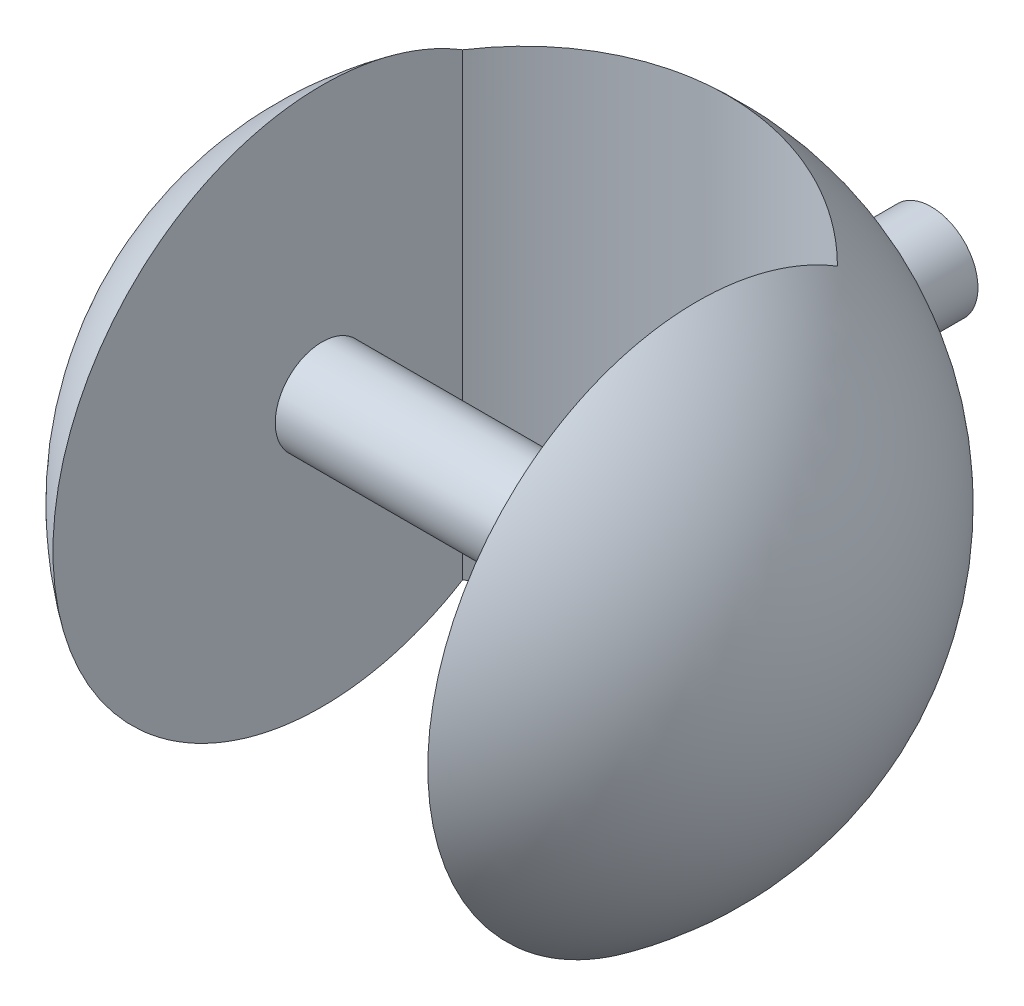
SolidWorks part; units mm, degrees
ref_plane "Front Plane" through (0, 0, 0) normal (0, 0, 1) x (1, 0, 0)
ref_plane "Top Plane" through (0, 0, 0) normal (0, 1, 0) x (1, 0, 0)
ref_plane "Right Plane" through (0, 0, 0) normal (1, 0, 0) x (0, 0, -1)
sketch "Sketch3" plane through (0, 0, 0) normal (0, 0, 1) x (1, 0, 0)
  line L0 (0, 136.0944) -> (0, -136.0944) construction
  line L1 (0, 70) -> (0, -70)
  arc A0 (0, 70) -> (0, -70) centre (0, 0) cw
  point P3 (0, 0)
  dimension "D1" = 70
revolve "Revolve1" add sketch "Sketch3" angle 360 about L0
sketch "Sketch4" plane through (0, 0, 0) normal (0, 1, 0) x (1, 0, 0)
  line L0 (-40, -70) -> (-40, 30)
  line L1 (-40, -70) -> (40, -70)
  line L3 (-40, 30) -> (40, 30)
  line L4 (40, -70) -> (40, 30)
  dimension "D2" = 100
extrude "Cut-Extrude1" cut sketch "Sketch4" against normal blind 200 and the other way blind 200
sketch "Sketch5" plane through (0, 0, -30) normal (0, 0, 1) x (1, 0, 0)
  circle A0 centre (0, 0) radius 10
extrude "Boss-Extrude1" add sketch "Sketch5" against normal blind 60
sketch "Sketch6" plane through (-40, 0, 0) normal (1, 0, 0) x (0, 0, -1)
  circle A0 centre (0, 0) radius 10
extrude "Boss-Extrude2" add sketch "Sketch6" along normal up to surface (80 mm away) up to face at (40, 0, 13.7228)
sketch "Sketch7" plane through (0, 0, 0) normal (0, 1, 0) x (1, 0, 0)
  line L0 (40, 30) -> (-40, 30)
  arc A0 (-40, 30) -> (40, 30) centre (0, -10) cw
extrude "Cut-Extrude2" cut sketch "Sketch7" against normal through all and the other way through all
